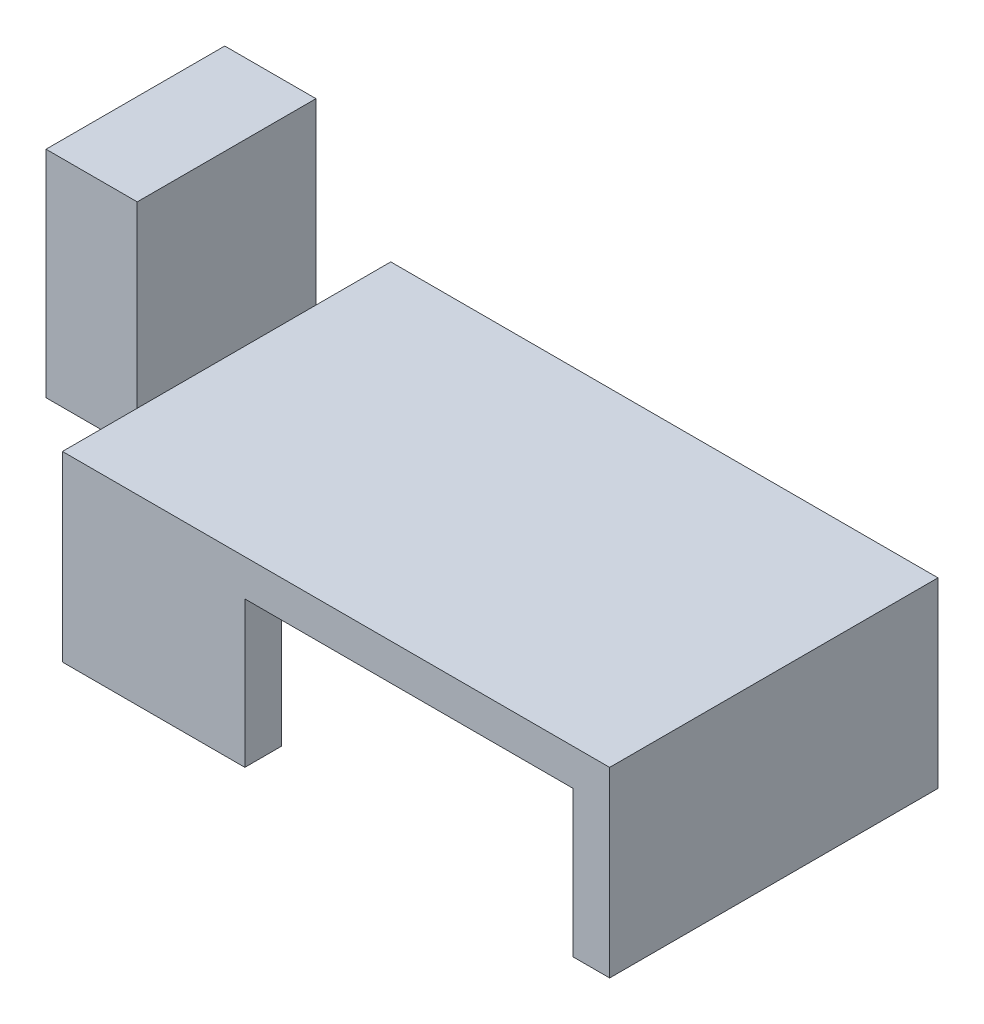
SolidWorks part; units mm, degrees
ref_plane "Front Plane" through (0, 0, 0) normal (0, 0, 1) x (1, 0, 0)
ref_plane "Top Plane" through (0, 0, 0) normal (0, 1, 0) x (1, 0, 0)
ref_plane "Right Plane" through (0, 0, 0) normal (1, 0, 0) x (0, 0, -1)
sketch "Sketch2" plane through (0, 0, 0) normal (0, 1, 0) x (1, 0, 0)
  line L1 (-9, 9) -> (9, 9)
  line L2 (-9, 9) -> (-9, -9)
  line L3 (-9, -9) -> (9, -9)
  line L4 (9, 9) -> (9, -9)
  line L5 (-9, 9) -> (9, -9) construction
  line L6 (-9, -9) -> (9, 9) construction
  point P0 (0, 0)
  dimension "D1" = 18
  dimension "D2" = 18
extrude "Boss-Extrude1" add sketch "Sketch2" along normal blind 2
sketch "Sketch3" plane through (0, 0, 0) normal (0, -1, 0) x (1, 0, 0)
  line L0 (9, 9) -> (9, -9) construction
  line L1 (-9, 9) -> (9, 9)
  line L2 (-9, 9) -> (-9, 7)
  line L3 (-9, 7) -> (9, 7)
  line L4 (9, 9) -> (9, 7)
  line L5 (-9, -9) -> (-9, 9) construction
  line L6 (9, -9) -> (-9, -9)
  line L7 (9, -9) -> (9, -7)
  line L8 (9, -7) -> (-9, -7)
  line L9 (-9, -9) -> (-9, -7)
  dimension "D1" = 2
  dimension "D2" = 2
extrude "Boss-Extrude2" add sketch "Sketch3" along normal blind 8
sketch "Sketch4" plane through (9, 0, 0) normal (1, 0, 0) x (0, 0, -1)
  line L0 (9, 2) -> (9, -8) construction
  line L1 (-9, 2) -> (9, 2)
  line L2 (-9, 2) -> (-9, 0)
  line L3 (-9, 0) -> (9, 0)
  line L4 (9, 2) -> (9, 0)
extrude "Boss-Extrude3" add sketch "Sketch4" along normal blind 12
sketch "Sketch5" plane through (0, 0, 0) normal (0, -1, 0) x (1, 0, 0)
  line L0 (21, -9) -> (9, -9) construction
  line L1 (21, 9) -> (19, 9)
  line L2 (21, 9) -> (21, -9)
  line L3 (21, -9) -> (19, -9)
  line L4 (19, 7) -> (19, -9)
  line L6 (9, 9) -> (19, 9)
  line L7 (9, 9) -> (9, 7)
  line L8 (9, 7) -> (19, 7)
  dimension "D1" = 2
  dimension "D2" = 2
extrude "Boss-Extrude4" add sketch "Sketch5" along normal blind 8
sketch "Sketch6" plane through (-9, 0, 0) normal (-1, 0, 0) x (0, 0, 1)
  line L0 (-9, 2) -> (-4.9, 2) construction
  line L1 (-9, 2) -> (9, 2) construction
  line L5 (-4.9, 2) -> (4.9, 2)
  line L6 (-4.9, 2) -> (-4.9, 0)
  line L7 (-4.9, 0) -> (4.9, 0)
  line L8 (4.9, 2) -> (4.9, 0)
  line L9 (-7, 0) -> (7, 0) construction
  dimension "D1" = 4.1
  dimension "D2" = 9.8
extrude "Boss-Extrude5" add sketch "Sketch6" along normal blind 5
extrude "Boss-Extrude7" add sketch "Sketch6<2>" along normal blind 5
sketch "Sketch6<2>" plane through (-9, 0, 0) normal (-1, 0, 0) x (0, 0, 1) same geometry as "Sketch6"
sketch "Sketch9" plane through (0, 2, 0) normal (0, 1, 0) x (1, 0, 0)
  line L1 (-14, 4.9) -> (-9, 4.9)
  line L2 (-14, 4.9) -> (-14, -4.9)
  line L3 (-14, -4.9) -> (-9, -4.9)
  line L4 (-9, 4.9) -> (-9, -4.9)
extrude "Boss-Extrude8" add sketch "Sketch9" along normal blind 9.8
sketch "Sketch10" plane through (0, 0, 7) normal (0, 0, -1) x (-1, 0, 0)
  line L1 (-19, 0) -> (-9, 0)
  line L2 (-19, 0) -> (-19, -8)
  line L3 (-19, -8) -> (-9, -8)
  line L4 (-9, 0) -> (-9, -8)
extrude "Cut-Extrude2" cut sketch "Sketch10" against normal blind 11.8
sketch "Sketch11" plane through (-9, 0, 0) normal (-1, 0, 0) x (0, 0, 1)
  line L1 (-9, -8) -> (-7, -8)
  line L2 (-9, -8) -> (-9, 0)
  line L3 (-9, 0) -> (-7, 0)
  line L4 (-7, -8) -> (-7, 0)
extrude "Cut-Extrude4" cut sketch "Sketch11" against normal blind 8
sketch "Sketch16" plane through (0, 0, 7) normal (0, 0, -1) x (-1, 0, 0)
  line L1 (1, 0) -> (9, 0)
  line L2 (1, 0) -> (1, -8)
  line L3 (1, -8) -> (9, -8)
  line L4 (9, 0) -> (9, -8)
extrude "Cut-Extrude5" cut sketch "Sketch16" against normal blind 8
sketch "Sketch17" plane through (-1, 0, 0) normal (-1, 0, 0) x (0, 0, 1)
  line L1 (-9, 0) -> (-7, 0)
  line L2 (-9, 0) -> (-9, -8)
  line L3 (-9, -8) -> (-7, -8)
  line L4 (-7, 0) -> (-7, -8)
  line L5 (9, -8) -> (7, -8)
  line L6 (9, -8) -> (9, 0)
  line L7 (9, 0) -> (7, 0)
  line L8 (7, -8) -> (7, 0)
extrude "Boss-Extrude11" add sketch "Sketch17" along normal blind 8
sketch "Sketch18" plane through (9, 0, 0) normal (1, 0, 0) x (0, 0, -1)
  line L1 (9, -8) -> (7, -8)
  line L2 (9, -8) -> (9, 0)
  line L3 (9, 0) -> (7, 0)
  line L4 (7, -8) -> (7, 0)
  line L5 (-7, -8) -> (-9, -8)
  line L6 (-7, -8) -> (-7, 0)
  line L7 (-7, 0) -> (-9, 0)
  line L8 (-9, -8) -> (-9, 0)
extrude "Cut-Extrude6" cut sketch "Sketch18" against normal blind 8
